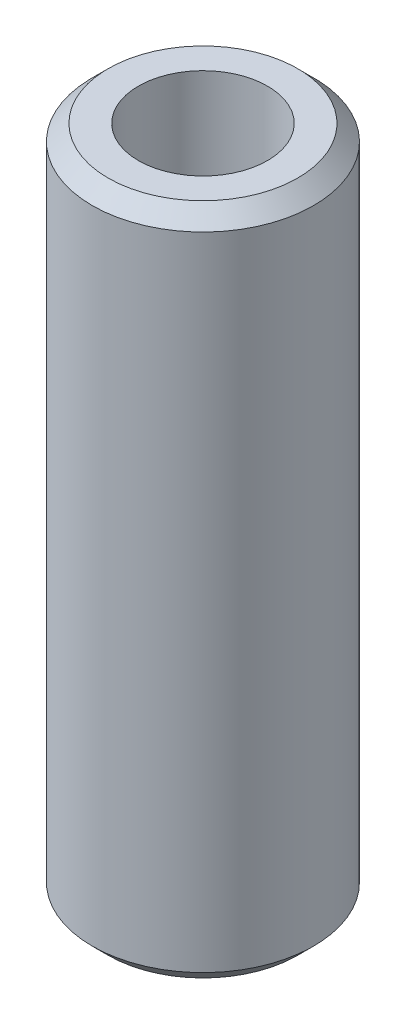
SolidWorks part; units mm, degrees
ref_plane "Front Plane" through (0, 0, 0) normal (0, 0, 1) x (1, 0, 0)
ref_plane "Top Plane" through (0, 0, 0) normal (0, 1, 0) x (1, 0, 0)
ref_plane "Right Plane" through (0, 0, 0) normal (1, 0, 0) x (0, 0, -1)
sketch "Sketch1" plane through (0, 0, 0) normal (0, 1, 0) x (1, 0, 0)
  circle A0 centre (0, 0) radius 25
  dimension "SHAFT_OD" = 50
extrude "Boss-Extrude1" add sketch "Sketch1" along normal blind 152.0266
sketch "Sketch2" plane through (0, 0, 0) normal (0, 1, 0) x (1, 0, 0)
  circle A0 centre (0, 0) radius 14.5811
  dimension "BORE_D" = 29.1621
extrude "Cut-Extrude1" cut sketch "Sketch2" along normal through all
chamfer "Chamfer1" distance 3.5871 angle 45 2 edges at (0, 152.0266, 25) (0, 0, 25)
